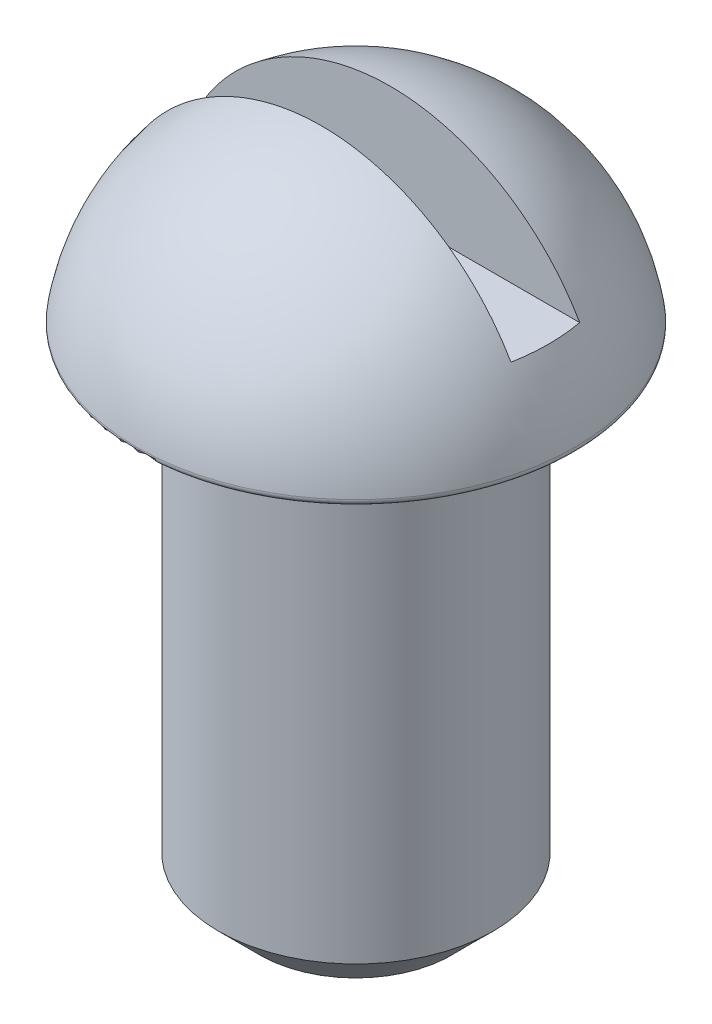
SolidWorks part; units mm, degrees
ref_plane "Спереди" through (0, 0, 0) normal (0, 0, 1) x (1, 0, 0)
ref_plane "Сверху" through (0, 0, 0) normal (0, 1, 0) x (1, 0, 0)
ref_plane "Справа" through (0, 0, 0) normal (1, 0, 0) x (0, 0, -1)
sketch "Эскиз1" plane through (0, 0, 0) normal (0, 0, 1) x (1, 0, 0)
  line L0 (0, 125.7632) -> (0, 0) construction
  line L1 (5, 87.2493) -> (8, 87.2493)
  line L2 (0, 94.2493) -> (0, 69.2493)
  line L3 (0, 94.2493) -> (1.25, 94.2493)
  line L4 (5, 87.2493) -> (5, 69.2493)
  line L6 (5, 69.2493) -> (0, 69.2493)
  arc A0 (1.25, 94.2493) -> (8, 87.2493) centre (-0.0384, 86.2524) cw
  dimension "D1" = 1.25
  dimension "D2" = 7
  dimension "D3" = 25
  dimension "D4" = 8.1
  dimension "D5" = 5
  dimension "D6" = 8
revolve "Повернуть1" add sketch "Эскиз1" angle 360 about L0
ref_axis "Ось4" through (0, 1.1667, 0) along (0, -1, 0)
sketch "Эскиз13" plane through (0, 94.2493, 0) normal (0, 1, 0) x (-1, 0, 0)
  line L1 (8, -1.25) -> (-8, -1.25)
  line L2 (8, -1.25) -> (8, 1.25)
  line L3 (8, 1.25) -> (-8, 1.25)
  line L4 (-8, -1.25) -> (-8, 1.25)
  dimension "D1" = 8
  dimension "D2" = 16
  dimension "D3" = 1.25
  dimension "D4" = 2.5
extrude "Вырез-Вытянуть9" cut sketch "Эскиз13" against normal blind 4
fillet "Скругление1" radius 0.2 1 edges at (-8, 87.2493, 0)
chamfer "Фаска1" distance 1.5 angle 45 1 edges at (-5, 69.2493, 0)
